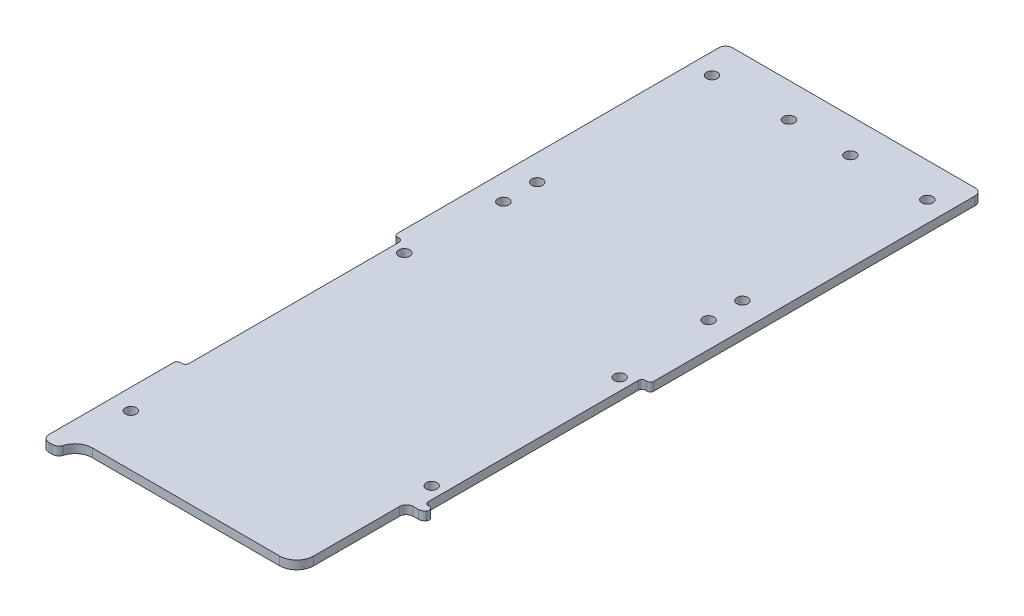
SolidWorks part; units mm, degrees
ref_plane "Front Plane" through (0, 0, 0) normal (0, 0, 1) x (1, 0, 0)
ref_plane "Top Plane" through (0, 0, 0) normal (0, 1, 0) x (1, 0, 0)
ref_plane "Right Plane" through (0, 0, 0) normal (1, 0, 0) x (0, 0, -1)
sketch "Sketch1" plane through (0, 0, 0) normal (0, 1, 0) x (1, 0, 0)
  line L0 (-39.9997, 0) -> (-39.9997, 114.3) construction
  line L1 (-47.625, 127) -> (47.625, 127)
  line L2 (-47.625, 127) -> (-47.625, -127)
  line L3 (-47.625, -127) -> (47.625, -127)
  line L4 (47.625, 127) -> (47.625, -127)
  line L5 (-47.625, 127) -> (47.625, -127) construction
  line L6 (-47.625, -127) -> (47.625, 127) construction
  line L7 (0, 0) -> (0, 127) construction
  line L8 (-39.9997, 0) -> (-39.9997, -101.6) construction
  line L9 (-39.9997, 0) -> (0, 0) construction
  line L10 (-41.275, -127) -> (-41.275, -120.65)
  line L11 (-41.275, -120.65) -> (41.275, -120.65)
  line L12 (41.275, -120.65) -> (41.275, -127)
  line L13 (-39.9997, 114.3) -> (-11.4247, 114.3) construction
  line L14 (39.9997, 114.3) -> (11.4247, 114.3) construction
  circle A0 centre (-39.9997, 114.3) radius 2.032
  circle A1 centre (-39.9997, 0) radius 2.032
  circle A2 centre (-39.9997, -101.6) radius 2.032
  circle A3 centre (39.9997, -101.6) radius 2.032
  circle A4 centre (39.9997, 0) radius 2.032
  circle A5 centre (39.9997, 114.3) radius 2.032
  circle A6 centre (-11.4247, 114.3) radius 2.032
  circle A7 centre (11.4247, 114.3) radius 2.032
  circle A8 centre (-39.9997, -69.85) radius 2.032
  circle A9 centre (39.9997, -69.85) radius 2.032
  point P0 (0, 0)
  dimension "D4" = 4.064
  dimension "D10" = 28.575
  dimension "D1" = 95.25
  dimension "D2" = 254
  dimension "D3" = 7.6253
  dimension "D5" = 12.7
  dimension "D6" = 25.4
  dimension "D7" = 6.35
  dimension "D8" = 6.35
  dimension "D9" = 6.35
  dimension "D11" = 69.85
extrude "Boss-Extrude1" add sketch "Sketch1" along normal blind 3.175 contours L4 L1 L2 L3 A4 A0 A1 A2 A3 A5 | A8 | A3 region at (0, 0, -2.6944) region at (39.9997, 0, 101.6) region at (-39.9997, 0, 69.85)
fillet "Fillet1" radius 2.54 4 edges at (-47.625, 1.5875, -127) (47.625, 1.5875, -127) (47.625, 1.5875, 127) (-47.625, 1.5875, 127)
fillet "Fillet2" radius 2.54 2 edges at (41.275, 1.5875, 127) (-41.275, 1.5875, 127)
fillet "Fillet3" radius 6.35 2 edges at (41.275, 1.5875, 120.65) (-41.275, 1.5875, 120.65)
sketch "Sketch2" plane through (0, 0, 0) normal (0, -1, 0) x (1, 0, 0)
  line L1 (43.815, 127) -> (45.085, 127) construction
  line L2 (40.6451, 123.5787) -> (40.6451, 79.8881)
  line L3 (40.6451, 79.8881) -> (47.625, 79.8881)
  line L11 (47.625, -124.46) -> (47.625, 124.46) construction
  line L12 (43.815, 127) -> (45.085, 127)
  line L13 (47.625, 79.8881) -> (47.625, 124.46)
  arc A0 (35.2956, 120.65) -> (41.3809, 125.1857) centre (35.2956, 127) ccw construction
  arc A1 (43.815, 127) -> (41.3809, 125.1857) centre (43.815, 124.46) ccw construction
  arc A2 (47.625, 124.46) -> (45.085, 127) centre (45.085, 124.46) ccw construction
  arc A3 (40.6451, 123.5787) -> (41.3809, 125.1857) centre (35.2956, 127) ccw
  arc A4 (43.815, 127) -> (41.3809, 125.1857) centre (43.815, 124.46) ccw
  arc A5 (47.625, 124.46) -> (45.085, 127) centre (45.085, 124.46) ccw
  dimension "D2" = 47.1119
  dimension "D1" = 6.9799
extrude "Cut-Extrude1" cut sketch "Sketch2" against normal through all
fillet "Fillet4" radius 6.35 1 edges at (40.6451, 1.5875, 123.5787)
fillet "Fillet5" radius 2.54 2 edges at (47.625, 1.5875, 79.8881) (40.6451, 1.5875, 79.8881)
sketch "Sketch3" plane through (0, 0, 0) normal (0, -1, 0) x (1, 0, 0)
  line L0 (-36.3033, -49.7791) -> (-39.9101, -49.7791) construction
  line L1 (-40.4181, -49.276) -> (-40.4181, -45.7043) construction
  line L2 (-35.7953, -45.7043) -> (-35.7953, -49.276) construction
  line L3 (-39.9101, -45.2013) -> (-36.3033, -45.2013) construction
  line L4 (-36.3033, -37.2027) -> (-39.9101, -37.2027) construction
  line L5 (-35.7953, -33.1279) -> (-35.7953, -36.6996) construction
  line L6 (-40.4181, -36.6996) -> (-40.4181, -33.1279) construction
  line L7 (-39.9101, -32.6249) -> (-36.3033, -32.6249) construction
  line L8 (36.2899, -32.6249) -> (39.8967, -32.6249) construction
  line L9 (40.4047, -33.1279) -> (40.4047, -36.6996) construction
  line L10 (39.8967, -37.2027) -> (36.2899, -37.2027) construction
  line L11 (35.7819, -36.6996) -> (35.7819, -33.1279) construction
  line L12 (36.2899, -45.2013) -> (39.8967, -45.2013) construction
  line L13 (35.7819, -49.276) -> (35.7819, -45.7043) construction
  line L14 (40.4047, -45.7043) -> (40.4047, -49.276) construction
  line L15 (39.8967, -49.7791) -> (36.2899, -49.7791) construction
  line L16 (-36.3033, -49.7791) -> (-39.9101, -49.7791)
  line L17 (-40.4181, -49.276) -> (-40.4181, -45.7043)
  line L18 (-35.7953, -45.7043) -> (-35.7953, -49.276)
  line L19 (-39.9101, -45.2013) -> (-36.3033, -45.2013)
  line L20 (-36.3033, -37.2027) -> (-39.9101, -37.2027)
  line L21 (-35.7953, -33.1279) -> (-35.7953, -36.6996)
  line L22 (-40.4181, -36.6996) -> (-40.4181, -33.1279)
  line L23 (-39.9101, -32.6249) -> (-36.3033, -32.6249)
  line L24 (36.2899, -32.6249) -> (39.8967, -32.6249)
  line L25 (40.4047, -33.1279) -> (40.4047, -36.6996)
  line L26 (39.8967, -37.2027) -> (36.2899, -37.2027)
  line L27 (35.7819, -36.6996) -> (35.7819, -33.1279)
  line L28 (36.2899, -45.2013) -> (39.8967, -45.2013)
  line L29 (35.7819, -49.276) -> (35.7819, -45.7043)
  line L30 (40.4047, -45.7043) -> (40.4047, -49.276)
  line L31 (39.8967, -49.7791) -> (36.2899, -49.7791)
  line L32 (-47.625, -25.836) -> (47.625, -25.836)
  line L33 (-47.625, -124.46) -> (-47.625, 124.46) construction
  line L34 (47.625, -124.46) -> (47.625, 77.3481) construction
  line L35 (0, -25.836) -> (0, -56.0686) construction
  line L1362 (-40.4181, -34.9138) -> (-35.7953, -34.9138)
  line L1857 (-38.1067, -32.6249) -> (-38.1067, -37.2027)
  line L1858 (-38.1067, -45.2013) -> (-38.1067, -49.7791)
  line L1859 (-40.4181, -47.4902) -> (-35.7953, -47.4902)
  circle A0 centre (-38.1067, -34.9138) radius 2.032
  circle A1 centre (-38.1067, -47.4902) radius 2.032
  circle A2 centre (38.1067, -47.4902) radius 2.032
  circle A3 centre (38.1067, -34.9138) radius 2.032
  ellipse E0 centre (-39.9101, -45.7043) end of major axis (-39.4021, -45.7043) minor radius 0.5031 (-39.9101, -45.2013) -> (-40.4181, -45.7043) ccw construction
  ellipse E1 centre (-39.9101, -49.276) end of major axis (-39.4021, -49.276) minor radius 0.5031 (-40.4181, -49.276) -> (-39.9101, -49.7791) ccw construction
  ellipse E6 centre (-36.3033, -49.276) end of major axis (-35.7953, -49.276) minor radius 0.5031 (-36.3033, -49.7791) -> (-35.7953, -49.276) ccw construction
  ellipse E7 centre (-36.3033, -45.7043) end of major axis (-35.7953, -45.7043) minor radius 0.5031 (-35.7953, -45.7043) -> (-36.3033, -45.2013) ccw construction
  ellipse E8 centre (-39.9101, -36.6996) end of major axis (-39.4021, -36.6996) minor radius 0.5031 (-40.4181, -36.6996) -> (-39.9101, -37.2027) ccw construction
  ellipse E9 centre (-36.3033, -36.6996) end of major axis (-35.7953, -36.6996) minor radius 0.5031 (-36.3033, -37.2027) -> (-35.7953, -36.6996) ccw construction
  ellipse E10 centre (-36.3033, -33.1279) end of major axis (-35.7953, -33.1279) minor radius 0.5031 (-35.7953, -33.1279) -> (-36.3033, -32.6249) ccw construction
  ellipse E11 centre (-39.9101, -33.1279) end of major axis (-39.4021, -33.1279) minor radius 0.5031 (-39.9101, -32.6249) -> (-40.4181, -33.1279) ccw construction
  ellipse E12 centre (39.8967, -33.1279) end of major axis (40.4047, -33.1279) minor radius 0.5031 (40.4047, -33.1279) -> (39.8967, -32.6249) ccw construction
  ellipse E13 centre (36.2899, -33.1279) end of major axis (36.7979, -33.1279) minor radius 0.5031 (36.2899, -32.6249) -> (35.7819, -33.1279) ccw construction
  ellipse E14 centre (39.8967, -36.6996) end of major axis (40.4047, -36.6996) minor radius 0.5031 (39.8967, -37.2027) -> (40.4047, -36.6996) ccw construction
  ellipse E15 centre (36.2899, -36.6996) end of major axis (36.7979, -36.6996) minor radius 0.5031 (35.7819, -36.6996) -> (36.2899, -37.2027) ccw construction
  ellipse E16 centre (36.2899, -45.7043) end of major axis (36.7979, -45.7043) minor radius 0.5031 (36.2899, -45.2013) -> (35.7819, -45.7043) ccw construction
  ellipse E17 centre (36.2899, -49.276) end of major axis (36.7979, -49.276) minor radius 0.5031 (35.7819, -49.276) -> (36.2899, -49.7791) ccw construction
  ellipse E18 centre (39.8967, -45.7043) end of major axis (40.4047, -45.7043) minor radius 0.5031 (40.4047, -45.7043) -> (39.8967, -45.2013) ccw construction
  ellipse E19 centre (39.8967, -49.276) end of major axis (40.4047, -49.276) minor radius 0.5031 (39.8967, -49.7791) -> (40.4047, -49.276) ccw construction
  ellipse E20 centre (-39.9101, -45.7043) end of major axis (-39.4021, -45.7043) minor radius 0.5031 (-39.9101, -45.2013) -> (-40.4181, -45.7043) ccw
  ellipse E21 centre (-39.9101, -49.276) end of major axis (-39.4021, -49.276) minor radius 0.5031 (-40.4181, -49.276) -> (-39.9101, -49.7791) ccw
  ellipse E22 centre (-36.3033, -49.276) end of major axis (-35.7953, -49.276) minor radius 0.5031 (-36.3033, -49.7791) -> (-35.7953, -49.276) ccw
  ellipse E23 centre (-36.3033, -45.7043) end of major axis (-35.7953, -45.7043) minor radius 0.5031 (-35.7953, -45.7043) -> (-36.3033, -45.2013) ccw
  ellipse E24 centre (-39.9101, -36.6996) end of major axis (-39.4021, -36.6996) minor radius 0.5031 (-40.4181, -36.6996) -> (-39.9101, -37.2027) ccw
  ellipse E25 centre (-36.3033, -36.6996) end of major axis (-35.7953, -36.6996) minor radius 0.5031 (-36.3033, -37.2027) -> (-35.7953, -36.6996) ccw
  ellipse E26 centre (-36.3033, -33.1279) end of major axis (-35.7953, -33.1279) minor radius 0.5031 (-35.7953, -33.1279) -> (-36.3033, -32.6249) ccw
  ellipse E27 centre (-39.9101, -33.1279) end of major axis (-39.4021, -33.1279) minor radius 0.5031 (-39.9101, -32.6249) -> (-40.4181, -33.1279) ccw
  ellipse E28 centre (39.8967, -33.1279) end of major axis (40.4047, -33.1279) minor radius 0.5031 (40.4047, -33.1279) -> (39.8967, -32.6249) ccw
  ellipse E29 centre (36.2899, -33.1279) end of major axis (36.7979, -33.1279) minor radius 0.5031 (36.2899, -32.6249) -> (35.7819, -33.1279) ccw
  ellipse E30 centre (39.8967, -36.6996) end of major axis (40.4047, -36.6996) minor radius 0.5031 (39.8967, -37.2027) -> (40.4047, -36.6996) ccw
  ellipse E31 centre (36.2899, -36.6996) end of major axis (36.7979, -36.6996) minor radius 0.5031 (35.7819, -36.6996) -> (36.2899, -37.2027) ccw
  ellipse E32 centre (36.2899, -45.7043) end of major axis (36.7979, -45.7043) minor radius 0.5031 (36.2899, -45.2013) -> (35.7819, -45.7043) ccw
  ellipse E33 centre (36.2899, -49.276) end of major axis (36.7979, -49.276) minor radius 0.5031 (35.7819, -49.276) -> (36.2899, -49.7791) ccw
  ellipse E34 centre (39.8967, -45.7043) end of major axis (40.4047, -45.7043) minor radius 0.5031 (40.4047, -45.7043) -> (39.8967, -45.2013) ccw
  ellipse E35 centre (39.8967, -49.276) end of major axis (40.4047, -49.276) minor radius 0.5031 (39.8967, -49.7791) -> (40.4047, -49.276) ccw
  dimension "D2" = 4.064
extrude "Cut-Extrude2" cut sketch "Sketch3" against normal through all contours A0 | A1 | A2 | A3
sketch "Sketch4" plane through (0, 3.175, 0) normal (0, 1, 0) x (1, 0, 0)
  line L11 (-47.625, 124.46) -> (-47.625, -124.46) construction
  line L12 (-47.625, -76.835) -> (-44.45, -76.835)
  line L13 (-47.625, -76.835) -> (-47.625, 3.81)
  line L15 (-47.625, 3.81) -> (-44.45, 3.81)
  line L16 (-44.45, -76.835) -> (-44.45, 3.81)
  line L17 (47.625, 124.46) -> (47.625, -77.3481) construction
  line L18 (47.625, -76.835) -> (44.45, -76.835)
  line L19 (47.625, -76.835) -> (47.625, 3.81)
  line L20 (47.625, 3.81) -> (44.45, 3.81)
  line L45 (44.45, -76.835) -> (44.45, 3.81)
  line L47 (43.1851, -79.8881) -> (45.085, -79.8881) construction
  dimension "D1" = 3.175
  dimension "D2" = 80.645
  dimension "D3" = 3.0531
extrude "Cut-Extrude3" cut sketch "Sketch4" against normal through all and the other way through all
fillet "Fillet6" radius 1.27 8 edges at (-44.45, 1.5875, -3.81) (-47.625, 1.5875, -3.81) (-47.625, 1.5875, 76.835) (-44.45, 1.5875, 76.835) (44.45, 1.5875, 76.835) (47.625, 1.5875, 76.835) (44.45, 1.5875, -3.81) (47.625, 1.5875, -3.81)
